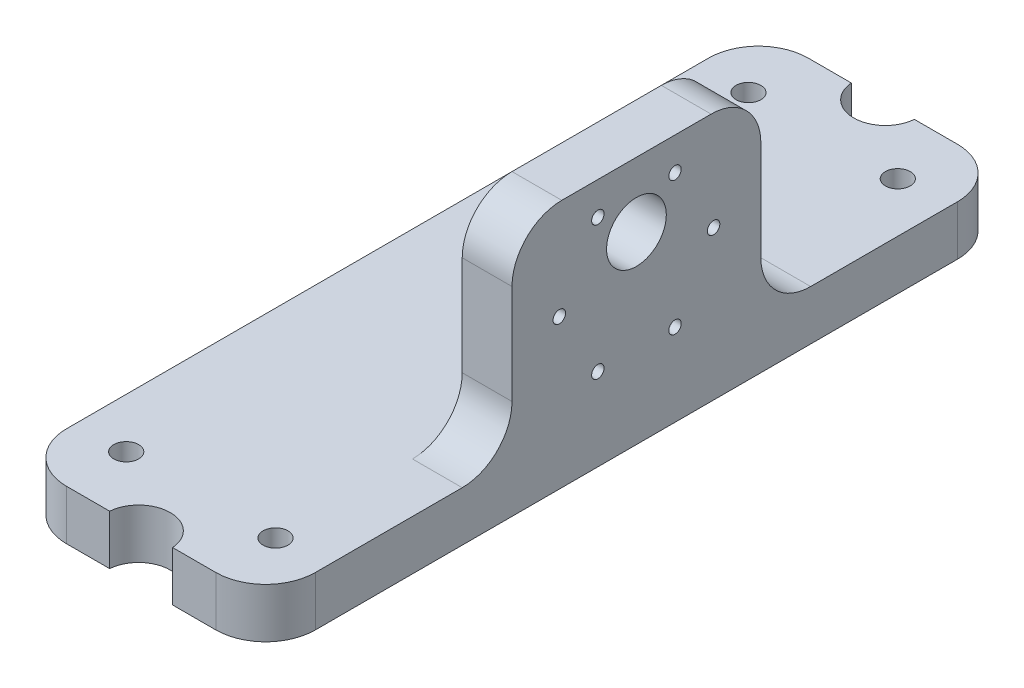
SolidWorks part; units mm, degrees
material "Nylon 101"
ref_plane "Front" through (0, 0, 0) normal (0, 0, 1) x (1, 0, 0)
ref_plane "Top" through (0, 0, 0) normal (0, 1, 0) x (1, 0, 0)
ref_plane "Right" through (0, 0, 0) normal (1, 0, 0) x (0, 0, -1)
sketch "Sketch1" plane through (0, 0, 0) normal (0, 1, 0) x (1, 0, 0)
  line L0 (-25, -75) -> (25, -75) construction
  line L1 (-15, 62.5) -> (15, 62.5) construction
  line L2 (0, -75) -> (0, 75) construction
  line L3 (-25, -75) -> (-25, 75)
  line L4 (25, -75) -> (25, 75)
  line L5 (25, 0) -> (0, 0) construction
  line L6 (25, 17) -> (97.2, 17)
  line L7 (25, 17) -> (25, -17)
  line L8 (25, -17) -> (97.2, -17)
  line L9 (97.2, 17) -> (97.2, -17)
  line L10 (-15, 62.5) -> (-15, -62.5) construction
  line L11 (-15, -62.5) -> (15, -62.5) construction
  line L12 (15, 62.5) -> (15, -62.5) construction
  line L13 (-25, -75.5) -> (25, -75.5)
  line L14 (-25, -74.5) -> (25, -74.5)
  line L15 (-25, 75.5) -> (25, 75.5)
  line L16 (-25, 74.5) -> (25, 74.5)
  circle A0 centre (0, 75) radius 6.35
  circle A1 centre (0, -75) radius 6.35
  arc A2 (-25, -75) -> (25, -75) centre (0, -75) ccw
  arc A3 (25, 75) -> (-25, 75) centre (0, 75) ccw
  circle A6 centre (-15, 62.5) radius 2.5
  circle A7 centre (-15, -62.5) radius 2.5
  circle A8 centre (15, -62.5) radius 2.5
  circle A9 centre (15, 62.5) radius 2.5
  point P8 (0, 0)
  point P24 (0, -62.5)
  dimension "D2" = 12.7
  dimension "D5" = 25
  dimension "D1" = 5
  dimension "D3" = 150
  dimension "D4" = 12.5
  dimension "D6" = 12.5
  dimension "D7" = 34
  dimension "D8" = 72.2
  dimension "D9" = 30
  dimension "D10" = 0.5
  dimension "D11" = 0.5
extrude "Boss-Extrude1" add sketch "Sketch1" along normal blind 10 contours A1 L14 L4 L16 A0 L3 A9 A8 A7 A6 region at (0, 0, 0)
sketch "Sketch2" plane through (0, 0, 0) normal (0, 1, 0) x (1, 0, 0)
  line L0 (25, -75) -> (25, 75) construction
  line L1 (25, 25) -> (15, 25)
  line L2 (25, 25) -> (25, -25)
  line L3 (25, -25) -> (15, -25)
  line L4 (15, 25) -> (15, -25)
  line L6 (25, 0) -> (0, 0) construction
  line L7 (25, 0) -> (0, 0) construction
  dimension "D1" = 50
  dimension "D2" = 10
extrude "Boss-Extrude2" add sketch "Sketch2" along normal blind 50
sketch "Sketch3" plane through (25, 0, 0) normal (1, 0, 0) x (0, 0, -1)
  line L0 (-25, 10) -> (25, 10) construction
  line L1 (0, 10) -> (0, 50) construction
  line L3 (-25, 50) -> (25, 50) construction
  circle A0 centre (0, 30) radius 15.5 construction
  circle A1 centre (0, 30) radius 18.4 construction
  circle A2 centre (-15.5, 30) radius 1.25
  circle A8 centre (0, 37) radius 3 construction
  circle A9 centre (0, 37) radius 6
  circle A10 centre (-7.75, 43.4234) radius 1.25
  circle A11 centre (7.75, 43.4234) radius 1.25
  circle A12 centre (15.5, 30) radius 1.25
  circle A13 centre (7.75, 16.5766) radius 1.25
  circle A14 centre (-7.75, 16.5766) radius 1.25
  dimension "D1" = 31
  dimension "D2" = 2.5
  dimension "D3" = 36.8
  dimension "D4" = 12
  dimension "D6" = 6
  dimension "D7" = 6
  dimension "D5" = 7
extrude "Cut-Extrude1" cut sketch "Sketch3" against normal blind 25
fillet "Fillet1" radius 10 8 edges at (-25, 5, -74.5) (25, 5, -74.5) (-25, 5, 74.5) (25, 5, 74.5) (20, 10, -25) (20, 50, -25) (20, 50, 25) (20, 10, 25)
